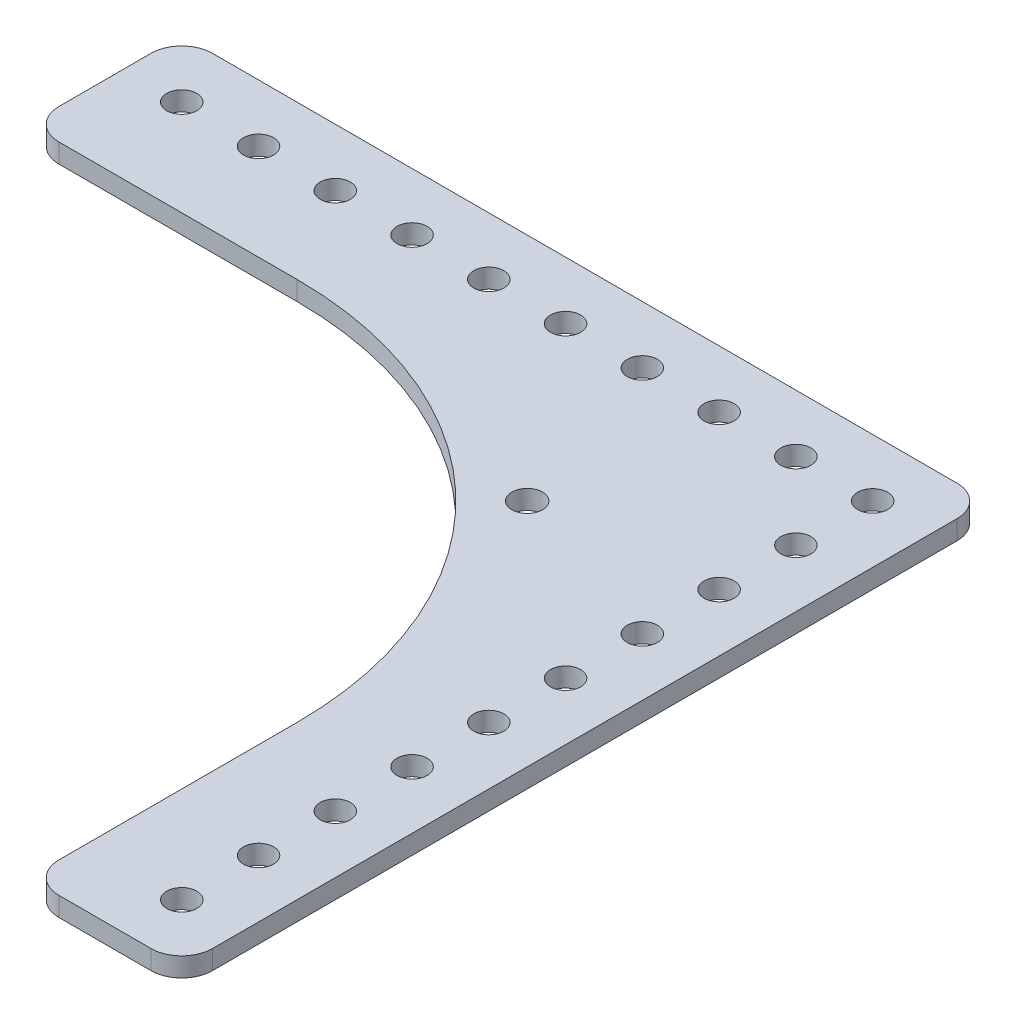
SolidWorks part; units mm, degrees
ref_plane "Front Plane" through (0, 0, 0) normal (0, 0, 1) x (1, 0, 0)
ref_plane "Top Plane" through (0, 0, 0) normal (0, 1, 0) x (1, 0, 0)
ref_plane "Right Plane" through (0, 0, 0) normal (1, 0, 0) x (0, 0, -1)
sketch "Sketch1" plane through (0, 0, 0) normal (0, 1, 0) x (1, 0, 0)
  line B0 (0, 63.5) -> (-33.02, 63.5)
  line B1 (-38.1, 68.58) -> (-38.1, 77.47)
  line B2 (-33.02, 82.55) -> (77.47, 82.55)
  line B3 (82.55, 77.47) -> (82.55, -33.02)
  line B4 (77.47, -38.1) -> (68.58, -38.1)
  line B5 (63.5, -33.02) -> (63.5, 0)
  arc B6 (0, 63.5) -> (63.5, 0) centre (0, 0) cw
  arc B7 (68.58, -38.1) -> (63.5, -33.02) centre (68.58, -33.02) cw
  arc B8 (82.55, -33.02) -> (77.47, -38.1) centre (77.47, -33.02) cw
  arc B9 (77.47, 82.55) -> (82.55, 77.47) centre (77.47, 77.47) cw
  arc B10 (-38.1, 77.47) -> (-33.02, 82.55) centre (-33.02, 77.47) cw
  arc B11 (-33.02, 63.5) -> (-38.1, 68.58) centre (-33.02, 68.58) cw
  circle B12 centre (-28.575, 73.025) radius 2.4892
  circle B13 centre (-15.875, 73.025) radius 2.4892
  circle B14 centre (-3.175, 73.025) radius 2.4892
  circle B15 centre (9.525, 73.025) radius 2.4892
  circle B16 centre (22.225, 73.025) radius 2.4892
  circle B17 centre (34.925, 73.025) radius 2.4892
  circle B18 centre (47.625, 73.025) radius 2.4892
  circle B19 centre (60.325, 73.025) radius 2.4892
  circle B20 centre (73.025, 73.025) radius 2.4892
  circle B21 centre (73.025, 60.325) radius 2.4892
  circle B22 centre (73.025, 47.625) radius 2.4892
  circle B23 centre (73.025, 34.925) radius 2.4892
  circle B24 centre (73.025, 22.225) radius 2.4892
  circle B25 centre (73.025, 9.525) radius 2.4892
  circle B26 centre (73.025, -3.175) radius 2.4892
  circle B27 centre (73.025, -15.875) radius 2.4892
  circle B28 centre (73.025, -28.575) radius 2.4892
  circle B29 centre (50.8, 50.8) radius 2.54
sketch_block_instance "Block-Bumper_Gussest-1"
sketch_block "Block-Bumper_Gussest" parameters "D1"=63.5, "D2"=5.08, "D3"=4.9784, "D8"=5.08, "D4"=9.525, "D5"=9.525, "D6"=12.7, "D7"=9.525, "D9"=31.75, "D10"=31.75
extrude "Boss-Extrude1" add sketch "Sketch1" along normal blind 3.175
sketch "Sketch3" plane through (0, 3.175, 0) normal (0, 1, 0) x (1, 0, 0)
  line L0 (-38.1, 69.85) -> (69.85, 69.85)
  line L1 (69.85, 69.85) -> (69.85, -38.1)
  line L2 (68.58, -38.1) -> (77.47, -38.1) construction
  line L4 (-39.37, 88.9) -> (83.82, 88.9)
  line L5 (88.9, 83.82) -> (88.9, -39.37)
  line L6 (63.5, 0) -> (63.5, -33.02)
  line L7 (68.58, -38.1) -> (77.47, -38.1)
  line L8 (82.55, -33.02) -> (82.55, 77.47)
  line L9 (77.47, 82.55) -> (-33.02, 82.55)
  line L10 (-38.1, 77.47) -> (-38.1, 68.58)
  line L11 (-33.02, 63.5) -> (0, 63.5)
  line L12 (63.5, 0) -> (63.5, -33.02)
  line L17 (-33.02, 63.5) -> (0, 63.5)
  line L19 (-38.1, 77.47) -> (-38.1, 68.58) construction
  line L20 (-33.02, 63.5) -> (-39.37, 63.5)
  line L23 (-44.45, 68.58) -> (-44.45, 83.82)
  line L24 (68.58, -38.1) -> (69.85, -38.1)
  line L26 (63.5, -33.02) -> (63.5, -39.37)
  line L27 (68.58, -44.45) -> (83.82, -44.45)
  line L29 (-38.1, 69.85) -> (-38.1, 68.58)
  circle A0 centre (50.8, 50.8) radius 2.54 construction
  circle A1 centre (50.8, 50.8) radius 2.54
  circle A2 centre (-28.575, 73.025) radius 2.4892 construction
  circle A3 centre (-15.875, 73.025) radius 2.4892 construction
  arc A5 (83.82, 88.9) -> (88.9, 83.82) centre (83.82, 83.82) cw
  arc A6 (63.5, 0) -> (0, 63.5) centre (0, 0) ccw
  arc A7 (63.5, -33.02) -> (68.58, -38.1) centre (68.58, -33.02) ccw
  arc A8 (77.47, -38.1) -> (82.55, -33.02) centre (77.47, -33.02) ccw
  arc A9 (82.55, 77.47) -> (77.47, 82.55) centre (77.47, 77.47) ccw
  arc A10 (-33.02, 82.55) -> (-38.1, 77.47) centre (-33.02, 77.47) ccw
  arc A11 (-38.1, 68.58) -> (-33.02, 63.5) centre (-33.02, 68.58) ccw
  arc A12 (63.5, 0) -> (0, 63.5) centre (0, 0) ccw
  circle A19 centre (-3.175, 73.025) radius 2.4892 construction
  circle A20 centre (9.525, 73.025) radius 2.4892 construction
  circle A21 centre (73.025, -28.575) radius 2.4892 construction
  circle A22 centre (73.025, -15.875) radius 2.4892 construction
  circle A23 centre (73.025, -3.175) radius 2.4892 construction
  circle A24 centre (73.025, 9.525) radius 2.4892 construction
  circle A25 centre (73.025, 22.225) radius 2.4892 construction
  circle A26 centre (73.025, 34.925) radius 2.4892 construction
  circle A27 centre (73.025, 47.625) radius 2.4892 construction
  circle A28 centre (73.025, 60.325) radius 2.4892 construction
  circle A29 centre (73.025, 73.025) radius 2.4892 construction
  circle A30 centre (60.325, 73.025) radius 2.4892 construction
  circle A31 centre (47.625, 73.025) radius 2.4892 construction
  circle A32 centre (34.925, 73.025) radius 2.4892 construction
  circle A33 centre (22.225, 73.025) radius 2.4892 construction
  circle A34 centre (73.025, -28.575) radius 2.4892
  circle A35 centre (73.025, -15.875) radius 2.4892
  circle A36 centre (73.025, -3.175) radius 2.4892
  circle A37 centre (73.025, 9.525) radius 2.4892
  circle A38 centre (73.025, 22.225) radius 2.4892
  circle A39 centre (73.025, 34.925) radius 2.4892
  circle A40 centre (73.025, 47.625) radius 2.4892
  circle A41 centre (73.025, 60.325) radius 2.4892
  circle A42 centre (73.025, 73.025) radius 2.4892
  circle A43 centre (60.325, 73.025) radius 2.4892
  circle A44 centre (47.625, 73.025) radius 2.4892
  circle A45 centre (34.925, 73.025) radius 2.4892
  circle A46 centre (22.225, 73.025) radius 2.4892
  circle A47 centre (9.525, 73.025) radius 2.4892
  circle A48 centre (-3.175, 73.025) radius 2.4892
  circle A49 centre (-15.875, 73.025) radius 2.4892
  circle A50 centre (-28.575, 73.025) radius 2.4892
  arc A51 (63.5, -33.02) -> (68.58, -38.1) centre (68.58, -33.02) ccw construction
  arc A52 (63.5, -33.02) -> (68.58, -38.1) centre (68.58, -33.02) ccw
  arc A53 (-38.1, 68.58) -> (-33.02, 63.5) centre (-33.02, 68.58) ccw construction
  arc A54 (-38.1, 68.58) -> (-33.02, 63.5) centre (-33.02, 68.58) ccw
  arc A55 (63.5, -39.37) -> (68.58, -44.45) centre (68.58, -39.37) ccw
  arc A56 (-39.37, 63.5) -> (-44.45, 68.58) centre (-39.37, 68.58) cw
  arc A57 (-39.37, 88.9) -> (-44.45, 83.82) centre (-39.37, 83.82) ccw
  arc A58 (83.82, -44.45) -> (88.9, -39.37) centre (83.82, -39.37) ccw
  point P21 (88.646, -44.4929)
  point P29 (88.646, -44.4929)
  point P30 (0, 0)
  point P92 (69.596, -38.1)
  point P93 (0, 0)
  point P94 (-38.1, 69.85)
  point P103 (88.264, -45.9468)
  point P104 (0, 0)
  point P105 (0, 0)
  line M20 (68.58, -38.1) -> (77.47, -38.1)
  arc M21 (77.47, -38.1) -> (82.55, -33.02) centre (77.47, -33.02) ccw
  line M22 (82.55, -33.02) -> (82.55, 77.47)
  arc M23 (82.55, 77.47) -> (77.47, 82.55) centre (77.47, 77.47) ccw
  line M24 (77.47, 82.55) -> (-33.02, 82.55)
  arc M25 (-33.02, 82.55) -> (-38.1, 77.47) centre (-33.02, 77.47) ccw
  line M26 (-38.1, 77.47) -> (-38.1, 68.58)
  circle M29 centre (-15.875, 73.025) radius 2.4892
  circle M30 centre (-28.575, 73.025) radius 2.4892
  circle M31 centre (-3.175, 73.025) radius 2.4892
  circle M32 centre (9.525, 73.025) radius 2.4892
  circle M33 centre (22.225, 73.025) radius 2.4892
  circle M34 centre (34.925, 73.025) radius 2.4892
  circle M35 centre (47.625, 73.025) radius 2.4892
  circle M36 centre (60.325, 73.025) radius 2.4892
  circle M37 centre (73.025, 73.025) radius 2.4892
  circle M38 centre (73.025, 60.325) radius 2.4892
  circle M39 centre (73.025, 47.625) radius 2.4892
  circle M40 centre (73.025, 34.925) radius 2.4892
  circle M41 centre (73.025, 22.225) radius 2.4892
  circle M42 centre (73.025, 9.525) radius 2.4892
  circle M43 centre (73.025, -3.175) radius 2.4892
  circle M44 centre (73.025, -15.875) radius 2.4892
  circle M45 centre (73.025, -28.575) radius 2.4892
  dimension "D6" = 5.08
  dimension "D9" = 5.08
  dimension "D10" = 5.08
  dimension "D2" = 6.35
  dimension "D3" = 6.35
  dimension "D4" = 19.05
  dimension "D5" = 6.35
  dimension "D7" = 6.35
  dimension "D8" = 19.05
  dimension "D1" = 0
extrude "Boss-Extrude2" add sketch "Sketch3" against normal up to surface (3.175 mm away) contours L0 L1 M20 M21 M22 M23 M24 M25 M26 M30 M32 M34 M36 M38 M40 M42 M44 M45 M43 M41 M39 M37 M35 M33 M31 M29 | L5 A5 L4 M25 M24 M23 M22 M21 | M44 | M45 | M43 | M41 | M42 | M40 | M39 | M38 | M30 | M31 | M32 | M33 | M34 | M35 | M36 | M37 | M29 region at (-36.3938, 3.175, -73.66) region at (-39.9859, 3.175, -69.215) region at (73.025, 3.175, 28.575) region at (73.025, 3.175, 15.875) region at (73.025, 3.175, 3.175) region at (73.025, 3.175, -9.525) region at (73.025, 3.175, -22.225) region at (73.025, 3.175, -34.925) region at (73.025, 3.175, -47.625) region at (73.025, 3.175, -60.325) region at (73.025, 3.175, -73.025) region at (60.325, 3.175, -73.025) region at (47.625, 3.175, -73.025) region at (34.925, 3.175, -73.025) region at (22.225, 3.175, -73.025) region at (9.525, 3.175, -73.025) region at (-3.175, 3.175, -73.025) region at (-15.875, 3.175, -73.025) region at (-28.575, 3.175, -73.025) up to face at (73.025, 0, 31.0642)
sketch "Sketch4" plane through (0, 3.175, 0) normal (0, 1, 0) x (1, 0, 0)
  line L0 (-44.45, 69.85) -> (69.85, 69.85)
  line L2 (69.85, 69.85) -> (69.85, -44.45)
  line L4 (-39.37, 63.5) -> (0, 63.5) construction
  line L5 (63.5, 0) -> (63.5, -39.37) construction
  line L6 (-44.45, 68.58) -> (-44.45, 83.82) construction
  line L7 (68.58, -44.45) -> (83.82, -44.45) construction
  line L8 (88.9, 83.82) -> (88.9, -39.37) construction
  line L9 (79.375, 79.375) -> (66.675, 79.375) construction
  line L10 (79.375, 79.375) -> (79.375, 66.675) construction
  circle A0 centre (79.375, 79.375) radius 2.4892
  circle A1 centre (66.675, 79.375) radius 2.4892
  circle A2 centre (53.975, 79.375) radius 2.4892
  circle A3 centre (41.275, 79.375) radius 2.4892
  circle A4 centre (28.575, 79.375) radius 2.4892
  circle A5 centre (15.875, 79.375) radius 2.4892
  circle A6 centre (3.175, 79.375) radius 2.4892
  circle A7 centre (-9.525, 79.375) radius 2.4892
  circle A8 centre (-22.225, 79.375) radius 2.4892
  circle A10 centre (79.375, 66.675) radius 2.4892
  circle A11 centre (79.375, 53.975) radius 2.4892
  circle A12 centre (79.375, 41.275) radius 2.4892
  circle A13 centre (79.375, 28.575) radius 2.4892
  circle A14 centre (79.375, 15.875) radius 2.4892
  circle A15 centre (79.375, 3.175) radius 2.4892
  circle A16 centre (79.375, -9.525) radius 2.4892
  circle A17 centre (79.375, -22.225) radius 2.4892
  circle A18 centre (-34.925, 79.375) radius 2.4892
  circle A19 centre (79.375, -34.925) radius 2.4892
  point P17 (0, 0)
  point P32 (0, 0)
  point P33 (0, 0)
  point P36 (0, 0)
  point P53 (0, 0)
  point P54 (0, 0)
  point P57 (0, 0)
  point P62 (0, 0)
  point P63 (0, 0)
  point P64 (0, 0)
  point P65 (0, 0)
  dimension "D3" = 9.525
  dimension "D5" = 4.9784
  dimension "D1" = 6.35
  dimension "D2" = 6.35
  dimension "D4" = 9.525
  dimension "D7" = 12.7
  dimension "D9" = 12.7
  dimension "D6" = 10
  dimension "D8" = 10
extrude "Cut-Extrude1" cut sketch "Sketch4" against normal through all contours A1 | A0 | A10 | A11 | A12 | A2 | A3 | A4 | A17 | A16 | A15 | A14 | A13 | A5 | A6 | A7 | A18 | A8 | A19 region at (79.375, 3.175, -79.375) region at (66.675, 3.175, -79.375) region at (53.975, 3.175, -79.375) region at (41.275, 3.175, -79.375) region at (28.575, 3.175, -79.375) region at (15.875, 3.175, -79.375) region at (3.175, 3.175, -79.375) region at (-9.525, 3.175, -79.375) region at (-22.225, 3.175, -79.375) region at (79.375, 3.175, -66.675) region at (79.375, 3.175, -53.975) region at (79.375, 3.175, -41.275) region at (79.375, 3.175, -28.575) region at (79.375, 3.175, -15.875) region at (79.375, 3.175, -3.175) region at (79.375, 3.175, 9.525) region at (79.375, 3.175, 22.225) region at (-34.925, 3.175, -79.375) region at (79.375, 3.175, 34.925)
